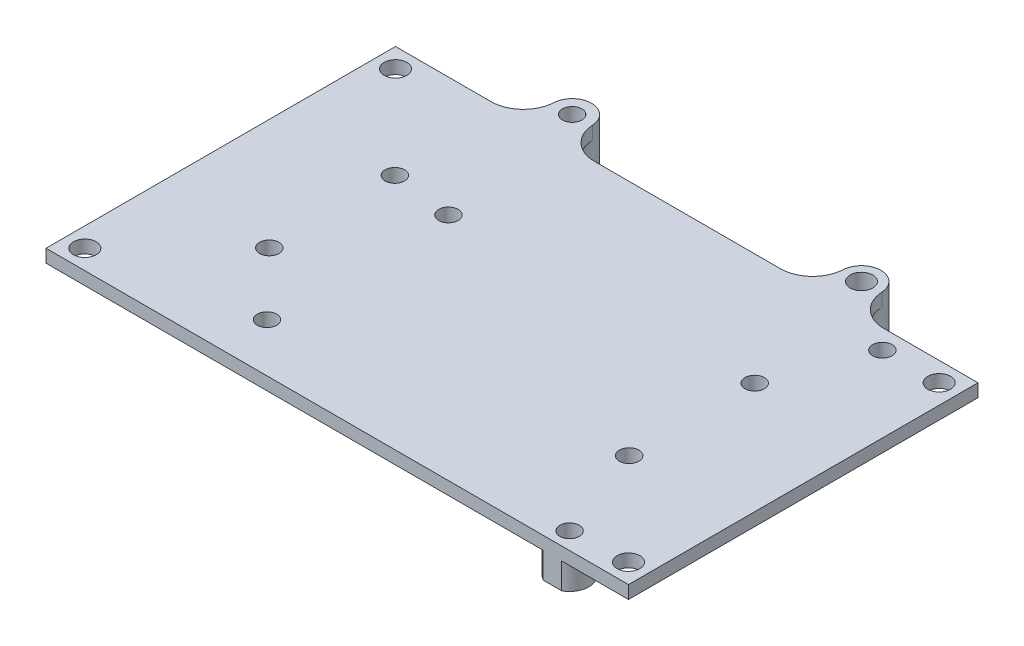
SolidWorks part; units mm, degrees
ref_plane "Front Plane" through (0, 0, 0) normal (0, 0, 1) x (1, 0, 0)
ref_plane "Top Plane" through (0, 0, 0) normal (0, 1, 0) x (1, 0, 0)
ref_plane "Right Plane" through (0, 0, 0) normal (1, 0, 0) x (0, 0, -1)
ref_plane "Plane1" through (0, 1, 0) normal (0, 1, 0) x (1, 0, 0)
sketch "Sketch2" plane through (0, 1, 0) normal (0, 1, 0) x (1, 0, 0)
  line L0 (-45, 0) -> (0, 0) construction
  line L5 (-45, -27) -> (0, -27)
  line L7 (-45, -24) -> (0, -24)
  line L10 (-45, 0) -> (0, 0)
  line L27 (0, 0) -> (0, -27)
  line L28 (-45, 0) -> (-45, -27)
  line L29 (-42, 0) -> (-42, -27)
  line L34 (0, 0) -> (0, -27) construction
  circle A1 centre (-27.8, -9.7) radius 1.5
  circle A5 centre (-27.8, -9.7) radius 3
  circle A10 centre (-42, -24) radius 1.75
  dimension "D17" = 6
  dimension "D22" = 3
  dimension "D3" = 9.7
  dimension "D4" = 17.2
  dimension "D5" = 3
  dimension "D6" = 27
  dimension "D7" = 45
  dimension "D8" = 3
extrude "Boss-Extrude1" add sketch "Sketch2" along normal blind 2 separate body contours A1 | L5 L27 L10 L28 | A10
sketch "Sketch5" plane through (0, 3, 0) normal (0, 1, 0) x (1, 0, 0)
  circle A0 centre (-27.8, -9.7) radius 3
  circle A1 centre (-27.8, -9.7) radius 1.5
extrude "Boss-Extrude2" add sketch "Sketch5" against normal blind 5
mirror "Mirror6" about plane through (0, 3, 0) normal (1, 0, 0) of bodies 117 114
mirror "Mirror7" about plane through (-45, 3, 0) normal (0, 0, -1) of bodies 115
sketch "Sketch8" plane through (0, 1, 0) normal (0, -1, 0) x (1, 0, 0)
  line L0 (31.8238, 27) -> (34.6857, 27)
  line L1 (-45, 27) -> (45, 27) construction
  circle A1 centre (33.2547, -23.9729) radius 1.5
  circle A3 centre (33.2547, 24.3633) radius 1.5
  circle A5 centre (-18.3708, -8.5472) radius 1.5
  circle A7 centre (-18.3708, 19.4848) radius 1.5
  circle A8 centre (-18.3708, -8.5472) radius 3
  circle A9 centre (-18.3708, 19.4848) radius 3
  circle A10 centre (33.2547, -23.9729) radius 3
  arc A11 (31.8238, 27) -> (34.6857, 27) centre (33.2547, 24.3633) ccw
extrude "Boss-Extrude3" add sketch "Sketch8" along normal blind 4 contours A9 | A8 | A10 | A11 L0 | A1 | A7 | A5 | A3
extrude "Cut-Extrude1" cut sketch "Sketch8<5>" against normal blind 4 contours A5 | A7 | A3 | A1 region at (-18.3708, 1, -8.5472) region at (-18.3708, 1, 19.4848)
sketch "Sketch8<5>" plane through (0, 1, 0) normal (0, -1, 0) x (1, 0, 0) same geometry as "Sketch8"
sketch "Sketch9" plane through (0, 1, 0) normal (0, -1, 0) x (1, 0, 0)
  line L0 (-25.2564, -31.5546) -> (-25.2564, -27)
  line L1 (-45, -27) -> (45, -27) construction
  line L2 (-19.2564, -31.5546) -> (-19.2564, -27)
  line L3 (19.4436, -31.5546) -> (19.4436, -27)
  line L4 (25.4436, -31.5546) -> (25.4436, -27)
  circle A2 centre (22.4436, -31.5546) radius 1.75
  circle A3 centre (-22.2564, -31.5546) radius 1.5
  circle A4 centre (-22.2564, -31.5546) radius 3
  circle A5 centre (22.4436, -31.5546) radius 3
  line M4 (-45, -27) -> (45, -27)
extrude "Boss-Extrude4" add sketch "Sketch9" against normal blind 2 contours A4 L2 L0 M4 | A4 A3 | A5 L4 L3 M4 | A5 A2 region at (22.4436, 1, -28.2012) region at (-22.2564, 1, -28.2012) region at (-22.2564, 1, -28.6394) region at (22.4436, 1, -28.6394)
extrude "Boss-Extrude5" add sketch "Sketch9<3>" along normal blind 8 contours A5 A2 | A4 A3 region at (-22.2564, 1, -34.4697) region at (22.4436, 1, -34.4697)
sketch "Sketch9<3>" plane through (0, 1, 0) normal (0, -1, 0) x (1, 0, 0) same geometry as "Sketch9"
fillet "Fillet1" radius 5 4 edges at (25.4436, 2, -27) (19.4436, 2, -27) (-25.2564, 2, -27) (-19.2564, 2, -27)
